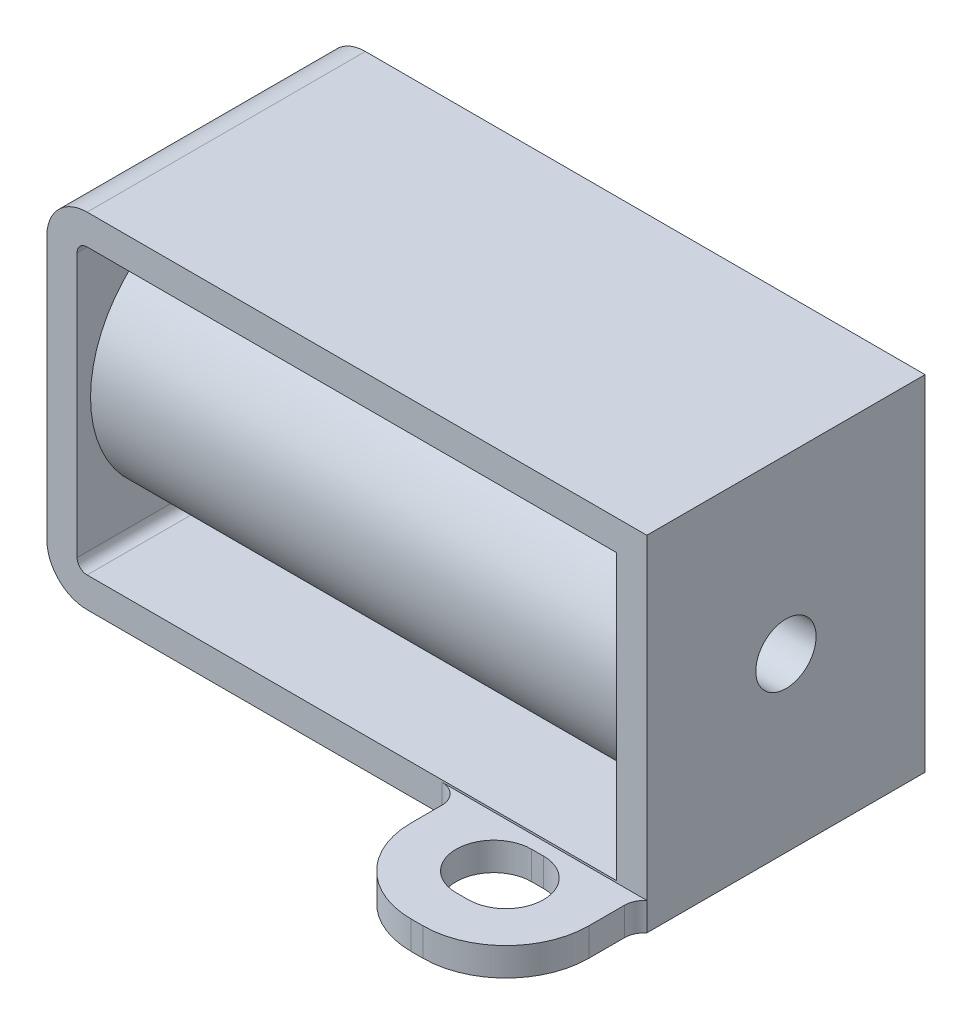
SolidWorks part; units mm, degrees
ref_plane "Front Plane" through (0, 0, 0) normal (0, 0, 1) x (1, 0, 0)
ref_plane "Top Plane" through (0, 0, 0) normal (0, 1, 0) x (1, 0, 0)
ref_plane "Right Plane" through (0, 0, 0) normal (1, 0, 0) x (0, 0, -1)
sketch "Sketch1" plane through (0, 0, 0) normal (1, 0, 0) x (0, 0, -1)
  line L1 (-6.92, 8.565) -> (6.92, 8.565)
  line L2 (-6.92, 8.565) -> (-6.92, -8.565)
  line L3 (-6.92, -8.565) -> (6.92, -8.565)
  line L4 (6.92, 8.565) -> (6.92, -8.565)
  line L5 (-6.92, 8.565) -> (6.92, -8.565) construction
  line L6 (-6.92, -8.565) -> (6.92, 8.565) construction
  point P0 (0, 0)
  dimension "D1" = 13.84
  dimension "D2" = 17.13
extrude "Boss-Extrude1" add sketch "Sketch1" along normal blind 29.84
sketch "Sketch2" plane through (0, 0, 0) normal (-1, 0, 0) x (0, 0, 1)
  circle A0 centre (0, 0) radius 1.5
  dimension "D1" = 3
extrude "Cut-Extrude1" cut sketch "Sketch2" against normal blind 29.84
sketch "Sketch3" plane through (0, -8.565, 0) normal (0, -1, 0) x (1, 0, 0)
  line L0 (8.565, -9.455) -> (7.965, -9.455) construction
  line L1 (8.565, -11.33) -> (7.965, -11.33)
  line L2 (8.565, -7.58) -> (7.965, -7.58)
  line L3 (6.09, -9.455) -> (10.44, -9.455) construction
  line L4 (0, 6.92) -> (0, -6.92)
  line L5 (0, -6.92) -> (29.84, -6.92)
  line L6 (29.84, -6.92) -> (29.84, 6.92)
  line L7 (29.84, 6.92) -> (0, 6.92)
  line L8 (0, 6.92) -> (0, -6.92)
  line L9 (0, -6.92) -> (29.84, -6.92)
  line L12 (8.565, -13.58) -> (7.965, -13.58)
  line L13 (8.565, -5.33) -> (7.965, -5.33)
  line L14 (6.09, -11.705) -> (10.44, -11.705)
  line L15 (29.84, 6.92) -> (0, 6.92) construction
  line L16 (29.84, 6.92) -> (29.84, -6.92) construction
  line L17 (3.84, -9.455) -> (3.84, -6.92)
  line L18 (12.69, -9.455) -> (12.69, -6.92)
  line L19 (16.665, -6.92) -> (16.665, 6.92) construction
  line L20 (16.665, 6.92) -> (16.665, 0) construction
  line L21 (16.665, 0) -> (29.84, 0) construction
  line L22 (6.09, 9.455) -> (10.44, 9.455) construction
  line L23 (12.69, 9.455) -> (12.69, 6.92) construction
  line L24 (3.84, 9.455) -> (3.84, 6.92) construction
  line L25 (6.09, 11.705) -> (10.44, 11.705) construction
  line L26 (8.565, 5.33) -> (7.965, 5.33) construction
  line L27 (8.565, 13.58) -> (7.965, 13.58) construction
  line L28 (8.565, 9.455) -> (7.965, 9.455) construction
  line L29 (8.565, 11.33) -> (7.965, 11.33) construction
  line L30 (8.565, 7.58) -> (7.965, 7.58) construction
  line L31 (24.765, 9.455) -> (25.365, 9.455) construction
  line L32 (24.765, 11.33) -> (25.365, 11.33)
  line L33 (24.765, 7.58) -> (25.365, 7.58)
  line L34 (27.24, 9.455) -> (22.89, 9.455) construction
  line L35 (24.765, 13.58) -> (25.365, 13.58)
  line L36 (24.765, 5.33) -> (25.365, 5.33)
  line L37 (27.24, 11.705) -> (22.89, 11.705)
  line L38 (29.49, 9.455) -> (29.49, 6.92)
  line L39 (20.64, 9.455) -> (20.64, 6.92)
  line L44 (29.84, 6.92) -> (0, 6.92)
  line L45 (29.84, -6.92) -> (29.84, 6.92) construction
  arc A0 (8.565, -11.33) -> (8.565, -7.58) centre (8.565, -9.455) ccw
  arc A1 (7.965, -7.58) -> (7.965, -11.33) centre (7.965, -9.455) ccw
  arc A2 (7.965, -5.33) -> (7.965, -13.58) centre (7.965, -9.455) ccw
  arc A3 (8.565, -13.58) -> (8.565, -5.33) centre (8.565, -9.455) ccw
  arc A4 (7.965, -5.33) -> (7.965, -13.58) centre (7.965, -9.455) ccw construction
  arc A5 (8.565, 13.58) -> (8.565, 5.33) centre (8.565, 9.455) cw construction
  arc A6 (7.965, 5.33) -> (7.965, 13.58) centre (7.965, 9.455) cw construction
  arc A7 (8.565, 11.33) -> (8.565, 7.58) centre (8.565, 9.455) cw construction
  arc A8 (7.965, 7.58) -> (7.965, 11.33) centre (7.965, 9.455) cw construction
  arc A9 (24.765, 11.33) -> (24.765, 7.58) centre (24.765, 9.455) ccw
  arc A10 (25.365, 7.58) -> (25.365, 11.33) centre (25.365, 9.455) ccw
  arc A11 (25.365, 5.33) -> (25.365, 13.58) centre (25.365, 9.455) ccw
  arc A12 (24.765, 13.58) -> (24.765, 5.33) centre (24.765, 9.455) ccw
  point P18 (8.265, -9.455)
  point P25 (0, 0)
  point P26 (3.84, -9.455)
  point P38 (8.265, 9.455)
  point P56 (25.065, 9.455)
  point P75 (0, 0)
  line M10 (0, 6.92) -> (0, -6.92)
  line M11 (0, -6.92) -> (29.84, -6.92)
  line M12 (29.84, -6.92) -> (29.84, 6.92)
  line M13 (29.84, 6.92) -> (0, 6.92)
  dimension "D7" = 4.35
  dimension "D2" = 2.25
  dimension "D3" = 20.5
  dimension "D4" = 26
  dimension "D5" = 12.69
  dimension "D6" = 3.75
  dimension "D8" = 9.2
  dimension "D1" = 0
extrude "Boss-Extrude2" add sketch "Sketch3" against normal blind 1.4 contours A12 L9 A2 L13 A3 A11 L36 M13 M10 M11 M12 | A3 L13 A2 M11 | L12 A3 A2 A1 L2 A0 L1 | A3 L18 L9 | A2 L9 L17 | L35 A12 L44 A11 A10 L33 A9 L32 | L44 A12 L36 A11 | A12 L39 M13 | A11 L38 M13 region at (14.8481, -8.565, 0) region at (20.8957, -8.565, 7.5396) region at (4.0957, -8.565, -7.5396) region at (20.9685, -8.565, 8.1508) region at (25.065, -8.565, 6.255) region at (8.265, -8.565, -6.255) region at (8.265, -8.565, -7.0308) region at (29.2343, -8.565, 7.5396) region at (12.4343, -8.565, -7.5396)
fillet "Fillet1" radius 2 2 edges at (0, 8.565, 0) (0, -8.565, 0)
fillet "Fillet2" radius 1 4 edges at (3.84, -7.865, -6.92) (12.69, -7.865, -6.92) (29.49, -7.865, 6.92) (20.64, -7.865, 6.92)
sketch "Sketch4" plane through (0, 0, 6.92) normal (0, 0, 1) x (1, 0, 0)
  line L8 (18.14, -5.665) -> (28.34, -5.665)
  line L9 (28.34, -7.065) -> (28.34, 7.065)
  line L10 (28.34, 7.065) -> (2, 7.065)
  line L11 (1.5, 6.565) -> (1.5, -6.565)
  line L12 (2, -7.065) -> (18.14, -7.065)
  line L13 (18.14, -7.065) -> (18.14, -5.665)
  line L14 (19.64, -7.165) -> (29.84, -7.165)
  line L15 (29.84, -7.165) -> (29.84, 8.565)
  line L25 (29.84, 8.565) -> (2, 8.565)
  line L26 (0, 6.565) -> (0, -6.565)
  line L27 (2, -8.565) -> (19.64, -8.565)
  line L28 (19.64, -8.565) -> (19.64, -7.165)
  line L29 (19.64, -7.165) -> (29.84, -7.165)
  line L30 (29.84, -7.165) -> (29.84, 8.565)
  line L31 (29.84, 8.565) -> (2, 8.565)
  line L32 (0, 6.565) -> (0, -6.565)
  line L33 (2, -8.565) -> (19.64, -8.565)
  line L34 (19.64, -8.565) -> (19.64, -7.165)
  line L35 (18.14, -7.065) -> (29.84, -7.065)
  line L36 (28.34, -5.665) -> (29.84, -5.665)
  line L37 (28.34, -5.665) -> (28.34, 7.065) construction
  arc A2 (2, 7.065) -> (1.5, 6.565) centre (2, 6.565) ccw
  arc A3 (1.5, -6.565) -> (2, -7.065) centre (2, -6.565) ccw
  arc A6 (2, 8.565) -> (0, 6.565) centre (2, 6.565) ccw
  arc A7 (0, -6.565) -> (2, -8.565) centre (2, -6.565) ccw
  arc A8 (2, 8.565) -> (0, 6.565) centre (2, 6.565) ccw
  arc A9 (0, -6.565) -> (2, -8.565) centre (2, -6.565) ccw
  dimension "D1" = 0
  dimension "D2" = 1.5
extrude "Cut-Extrude2" cut sketch "Sketch4" against normal through all contours L11 A3 L12 L13 L8 L9 L10 A2 | L13 L35 L9 L8 region at (14.5983, 0.2491, 6.92) region at (23.24, -6.365, 6.92)
sketch "Sketch5" plane through (1.5, 0, 0) normal (1, 0, 0) x (0, 0, -1)
  circle A2 centre (0, 0) radius 6.25
  circle A3 centre (0, 0) radius 1.5 construction
  circle A4 centre (0, 0) radius 1.5
  circle M10 centre (0, 0) radius 1.5
  dimension "D1" = 12.5
extrude "Boss-Extrude3" add sketch "Sketch5" along normal up to surface (26.84 mm away) contours A2 M10 region at (1.5, 0, 6.0732) up to face at (28.34, 0, -1.5)
